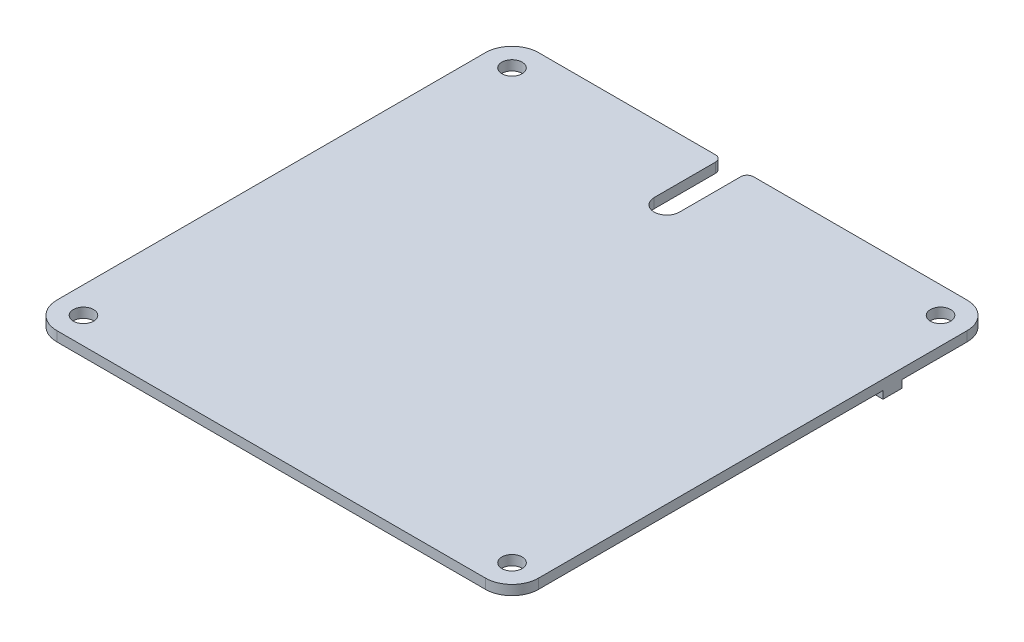
SolidWorks part; units mm, degrees
ref_plane "Front Plane" through (0, 0, 0) normal (0, 0, 1) x (1, 0, 0)
ref_plane "Top Plane" through (0, 0, 0) normal (0, 1, 0) x (1, 0, 0)
ref_plane "Right Plane" through (0, 0, 0) normal (1, 0, 0) x (0, 0, -1)
sketch "Base plate" plane through (0, 0, 0) normal (0, 1, 0) x (1, 0, 0)
  line L0 (-2.9, 38.1) -> (-2.9, 27.4) construction
  line L1 (-33.9, -38.1) -> (33.9, -38.1)
  line L2 (-38.1, -33.9) -> (-38.1, 33.9)
  line L3 (-33.9, 38.1) -> (33.9, 38.1)
  line L4 (38.1, -33.9) -> (38.1, 33.9)
  line L5 (-38.1, -38.1) -> (38.1, 38.1) construction
  line L6 (-38.1, 38.1) -> (38.1, -38.1) construction
  line L7 (-0.9, 38.1) -> (-0.9, 27.4)
  line L8 (-4.9, 38.1) -> (-4.9, 27.4)
  circle A0 centre (-33.9, 33.9) radius 1.6
  circle A1 centre (33.9, 33.9) radius 1.6
  circle A2 centre (33.9, -33.9) radius 1.6
  circle A3 centre (-33.9, -33.9) radius 1.6
  arc A4 (-33.9, -38.1) -> (-38.1, -33.9) centre (-33.9, -33.9) cw
  arc A5 (33.9, -38.1) -> (38.1, -33.9) centre (33.9, -33.9) ccw
  arc A6 (33.9, 38.1) -> (38.1, 33.9) centre (33.9, 33.9) cw
  arc A7 (-38.1, 33.9) -> (-33.9, 38.1) centre (-33.9, 33.9) cw
  arc A9 (-4.9, 27.4) -> (-0.9, 27.4) centre (-2.9, 27.4) ccw
  point P0 (0, 0)
  dimension "D2" = 3.2
  dimension "D4" = 4.2
  dimension "D5" = 2
  dimension "D6" = 12.7
  dimension "D1" = 76.2
  dimension "D3" = 4.2
  dimension "D7" = 39
extrude "凸台-拉伸1" add sketch "Base plate" along normal blind 1.55 contours A9 L8 L3 A7 L2 A4 L1 A5 L4 A6 L7 A3 A2 A1 A0 region at (0.0249, 0, 0.2747)
fillet "圆角1" radius 1 2 edges at (-4.9, 0.775, -38.1) (-0.9, 0.775, -38.1)
sketch "草图1" plane through (0, 0, 0) normal (0, -1, 0) x (1, 0, 0)
  line L0 (456, 1824) -> (2280, 1824) construction
  line L1 (-33.9, -33.9) -> (33.9, -33.9) construction
  line L2 (38.1, 33.9) -> (38.1, -33.9) construction
  line L3 (-0.35, 10.415) -> (-38.1, 10.415) construction
  line L4 (-38.1, 33.9) -> (-38.1, -33.9) construction
  line L5 (-33.9, 38.1) -> (33.9, 38.1) construction
  line L6 (11.4, 2) -> (11.4, -7.4) construction
  line L7 (13.9, 2) -> (13.9, -7.4)
  line L8 (8.9, 2) -> (8.9, -7.4)
  line L9 (24.1, -0.16) -> (24.1, -5.24) construction
  line L10 (26.6, -0.16) -> (26.6, -5.24)
  line L11 (21.6, -0.16) -> (21.6, -5.24)
  line L12 (24.1, -2.7) -> (11.4, -2.7) construction
  line L13 (19.6, 21.71) -> (19.6, 14.09) construction
  line L14 (22.1, 21.71) -> (22.1, 14.09)
  line L15 (17.1, 21.71) -> (17.1, 14.09)
  line L16 (30.8, -22.1) -> (38.1, -22.1) construction
  line L17 (30.8, -20.6) -> (38.1, -20.6)
  line L18 (30.8, -23.6) -> (38.1, -23.6)
  line L19 (27.7, 17.9) -> (19.6, 17.9) construction
  line L24 (16.7, -15.1) -> (31.9, -15.1) construction
  line L25 (38.1, -20.6) -> (38.1, -23.6)
  line L26 (24.4, -28.1) -> (24.4, -33.1) construction
  line L27 (26.65, -28.1) -> (26.65, -33.1)
  line L28 (22.15, -28.1) -> (22.15, -33.1)
  line L29 (20.8, -22.1) -> (19.4, -25.1) construction
  line L30 (22.8389, -23.0515) -> (21.4389, -26.0515)
  line L31 (18.7611, -21.1485) -> (17.3611, -24.1485)
  line L32 (19.4, -36.1) -> (19.4, -38.1) construction
  line L33 (0.1, -38.1) -> (33.9, -38.1) construction
  line L34 (21.65, -36.1) -> (21.65, -38.1)
  line L35 (17.15, -36.1) -> (17.15, -38.1)
  line L36 (17.15, -38.1) -> (21.65, -38.1)
  line L37 (24.4, -30.6) -> (19.4, -30.6) construction
  line L38 (19.4, -25.1) -> (19.4, -36.1) construction
  line L39 (30.8, -22.1) -> (20.8, -22.1) construction
  line L40 (18.348, -34.1111) -> (22.15, -32.1)
  line L41 (25.452, -35.0889) -> (21.65, -37.1)
  line L42 (18.348, -27.0889) -> (22.15, -29.1)
  line L43 (25.452, -26.1111) -> (22.2111, -24.3968)
  line L44 (0.1, -38.1) -> (33.9, -38.1) construction
  circle A0 centre (-22.7, 23.9) radius 3.25
  circle A1 centre (-0.35, 10.415) radius 3.25
  circle A2 centre (-22.7, -3.07) radius 3.25
  circle A3 centre (-17.96, -15.36) radius 3.5
  circle A4 centre (-5.01, -15.36) radius 3.5
  arc A8 (13.9, 2) -> (8.9, 2) centre (11.4, 2) ccw
  arc A9 (8.9, -7.4) -> (13.9, -7.4) centre (11.4, -7.4) ccw
  arc A10 (26.6, -0.16) -> (21.6, -0.16) centre (24.1, -0.16) ccw
  arc A11 (21.6, -5.24) -> (26.6, -5.24) centre (24.1, -5.24) ccw
  circle A12 centre (27.7, 17.9) radius 2.5
  arc A13 (22.1, 21.71) -> (17.1, 21.71) centre (19.6, 21.71) ccw
  arc A14 (17.1, 14.09) -> (22.1, 14.09) centre (19.6, 14.09) ccw
  arc A15 (30.8, -20.6) -> (30.8, -23.6) centre (30.8, -22.1) ccw
  circle A21 centre (16.7, -15.1) radius 2.4
  circle A22 centre (31.9, -15.1) radius 2.4
  circle A23 centre (33.9, -33.9) radius 1.6 construction
  circle A24 centre (33.9, 33.9) radius 1.6 construction
  arc A25 (26.65, -28.1) -> (22.15, -28.1) centre (24.4, -28.1) ccw
  arc A26 (22.15, -33.1) -> (26.65, -33.1) centre (24.4, -33.1) ccw
  arc A27 (22.8389, -23.0515) -> (18.7611, -21.1485) centre (20.8, -22.1) ccw
  arc A28 (17.3611, -24.1485) -> (21.4389, -26.0515) centre (19.4, -25.1) ccw
  arc A29 (21.65, -36.1) -> (17.15, -36.1) centre (19.4, -36.1) ccw
  point P21 (11.4, -2.7)
  point P26 (24.1, -2.7)
  point P39 (19.6, 17.9)
  point P61 (24.4, -30.6)
  point P70 (20.1, -23.6)
  point P95 (-38.1, 10.415)
  line M4 (0.1, -38.1) -> (33.9, -38.1)
  line M6 (38.1, -33.9) -> (38.1, 33.9)
  dimension "D1" = 6.5
  dimension "D7" = 7
  dimension "D10" = 2.5
  dimension "D11" = 5
  dimension "D12" = 2.5
  dimension "D13" = 4.8
  dimension "D20" = 6.2
  dimension "D21" = 11.8
  dimension "D24" = 5.08
  dimension "D31" = 2.25
  dimension "D33" = 9.5
  dimension "D2" = 26.97
  dimension "D3" = 15.4
  dimension "D4" = 22.35
  dimension "D5" = 14.2
  dimension "D6" = 12.95
  dimension "D8" = 4.74
  dimension "D9" = 12.29
  dimension "D14" = 15.2
  dimension "D15" = 8.1
  dimension "D16" = 7.62
  dimension "D17" = 9.4
  dimension "D18" = 12.7
  dimension "D19" = 3
  dimension "8.6" = 8.8
  dimension "D22" = 18.8
  dimension "D23" = 14
  dimension "D25" = 31.2
  dimension "D26" = 16
  dimension "D27" = 18.5
  dimension "D28" = 5
  dimension "D29" = 4.5
  dimension "D30" = 5
  dimension "D32" = 11
  dimension "D34" = 5
  dimension "D35" = 10
extrude "凸台-拉伸2" add sketch "草图1" along normal blind 4.5 contours A2 | A3 | A4 | A1 | A0 region at (-22.7, 0, 23.9) region at (-0.35, 0, 10.415) region at (-22.7, 0, -3.07) region at (-17.96, 0, -15.36) region at (-5.01, 0, -15.36)
extrude "凸台-拉伸3" add sketch "草图1<3>" along normal blind 2 contours L8 A9 L7 A8 | L11 A11 L10 A10 | A21 | A22 region at (11.4, 0, -2.7) region at (24.1, 0, -2.7) region at (16.7, 0, -15.1) region at (31.9, 0, -15.1)
sketch "草图1<3>" plane through (0, 0, 0) normal (0, -1, 0) x (1, 0, 0) same geometry as "草图1"
extrude "凸台-拉伸4" add sketch "草图1<4>" along normal blind 1.2 contours L31 A28 L30 A27 | A26 L27 A25 L28 | L34 A29 L35 M4 | L15 A14 L14 A13 | A12 | L17 A15 L18 M6 region at (19.6, 0, 17.9) region at (33.8543, 0, -22.1) region at (24.4, 0, -30.6) region at (20.1, 0, -23.6) region at (19.4, 0, -36.183) region at (27.7, 0, 17.9)
sketch "草图1<4>" plane through (0, 0, 0) normal (0, -1, 0) x (1, 0, 0) same geometry as "草图1"
